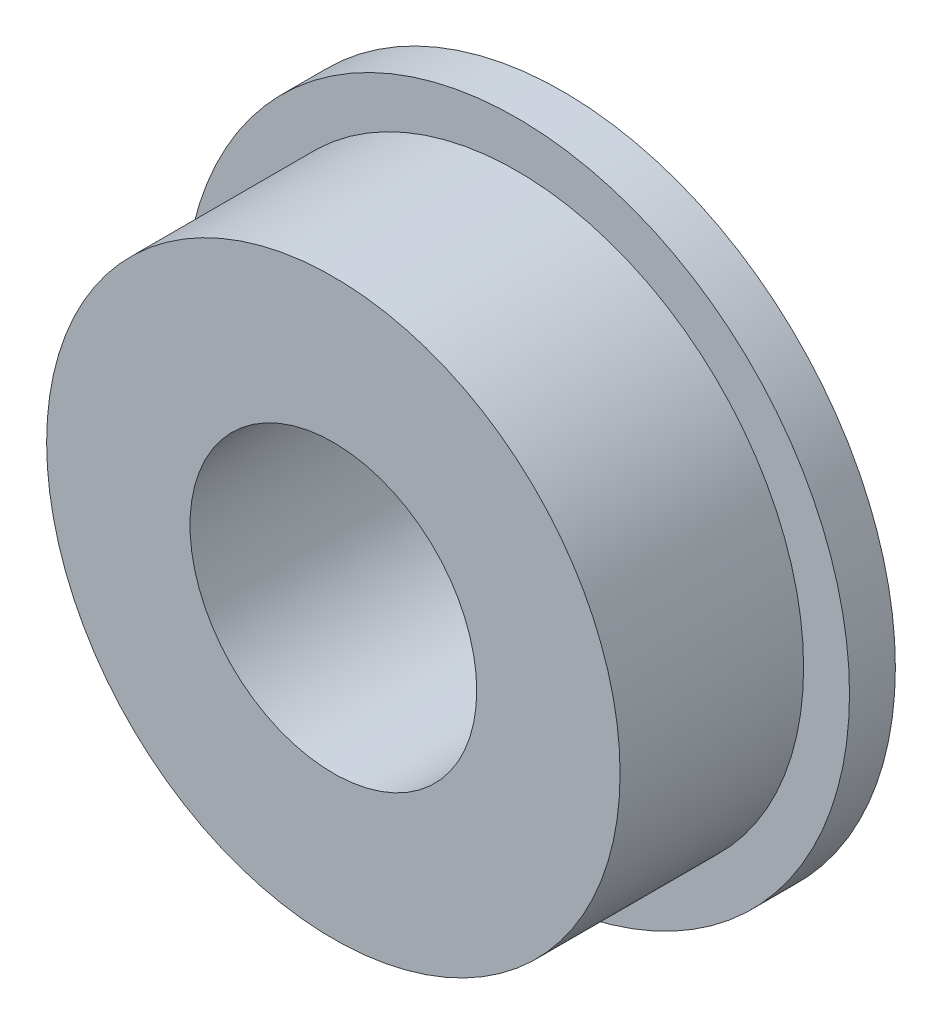
SolidWorks part; units mm, degrees
ref_plane "前视基准面" through (0, 0, 0) normal (0, 0, 1) x (1, 0, 0)
ref_plane "上视基准面" through (0, 0, 0) normal (0, 1, 0) x (1, 0, 0)
ref_plane "右视基准面" through (0, 0, 0) normal (1, 0, 0) x (0, 0, -1)
other "Configuration Table"
sketch "草图1" plane through (0, 0, 0) normal (0, 0, 1) x (1, 0, 0)
  circle A0 centre (0, 0) radius 2.5
  circle A1 centre (0, 0) radius 5
  circle A2 centre (0, 0) radius 5.8
  dimension "D1" = 10
  dimension "D2" = 11.6
  dimension "D3" = 5
extrude "凸台-拉伸1" add sketch "草图1" along normal blind 4 contours A1 A0 region at (-4.8586, 0, 0)
extrude "凸台-拉伸2" add sketch "草图1<3>" along normal blind 0.8 contours A2 A1 region at (-5.636, 0, 0)
sketch "草图1<3>" plane through (0, 0, 0) normal (0, 0, 1) x (1, 0, 0) same geometry as "草图1"
